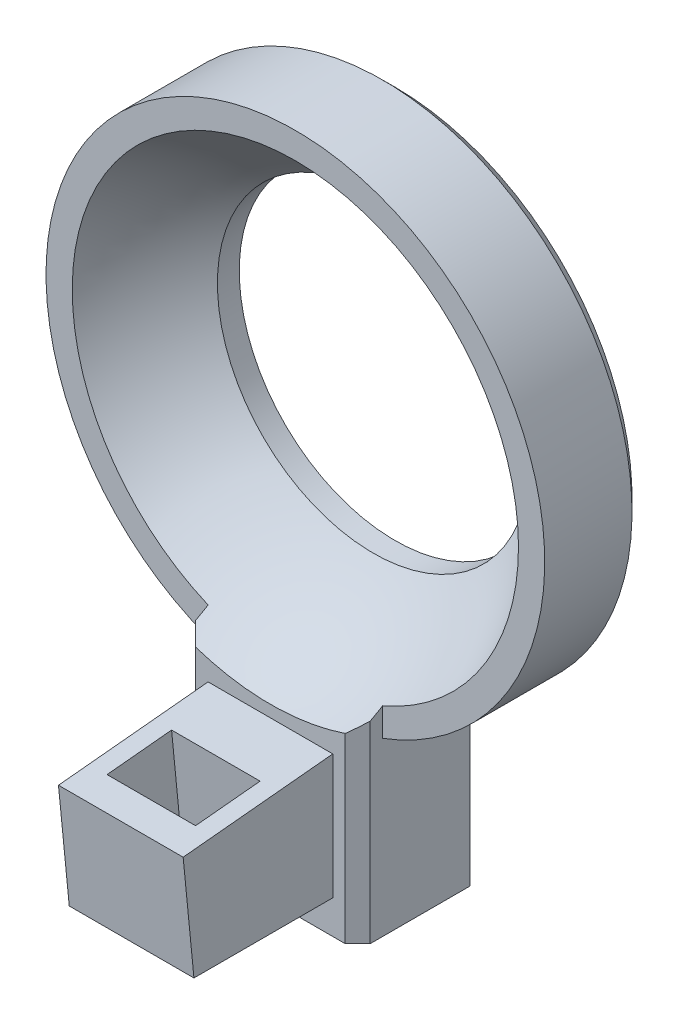
SolidWorks part; units mm, degrees
material "ABS"
ref_plane "Front Plane" through (0, 0, 0) normal (0, 0, 1) x (1, 0, 0)
ref_plane "Top Plane" through (0, 0, 0) normal (0, 1, 0) x (1, 0, 0)
ref_plane "Right Plane" through (0, 0, 0) normal (1, 0, 0) x (0, 0, -1)
sketch "Sketch1" plane through (0, 0, 0) normal (0, 0, 1) x (1, 0, 0)
  circle A0 centre (0, 0) radius 12.5
  circle A1 centre (0, 0) radius 20
  dimension "D1" = 40
  dimension "D2" = 25
extrude "Boss-Extrude1" add sketch "Sketch1" along normal blind 8
ref_axis "Axis1" through (0, 0, 8) along (0, 0, -1)
sketch "Sketch3" plane through (0, 0, 0) normal (0, 0, 1) x (1, 0, 0)
  line L0 (0, 0) -> (0, -32.5) construction
  line L1 (-7, -18.735) -> (-7, -32.5)
  line L2 (-7, -32.5) -> (7, -32.5)
  line L3 (7, -18.735) -> (7, -32.5)
  line L4 (-7, -18.735) -> (-7, -15.235)
  line L5 (-7, -15.235) -> (7, -15.235)
  line L6 (7, -15.235) -> (7, -18.735)
  circle A0 centre (0, 0) radius 20 construction
  dimension "D1" = 32.5
  dimension "D2" = 14
  dimension "D3" = 3.5
extrude "Boss-Extrude2" add sketch "Sketch3" along normal blind 10
sketch "Sketch2" plane through (0, 0, 0) normal (0, 1, 0) x (1, 0, 0)
  line L0 (0, -8) -> (0, 0) construction
  line L1 (0, -38.5) -> (0, 2.5)
  arc A0 (0, 2.5) -> (0, -38.5) centre (0, -18) ccw
  dimension "D1" = 41
  dimension "D2" = 18
revolve "Cut-Revolve2" cut sketch "Sketch2" angle 360 about axis through (0, 0, 8) along (0, 0, -1)
sketch "Sketch4" plane through (0, -32.5, 0) normal (0, -1, 0) x (1, 0, 0)
  line L0 (0, 10) -> (0, 0) construction
  line L8 (-7, 10) -> (7, 10) construction
  line L10 (-3.15, 8.15) -> (3.15, 8.15)
  line L11 (-3.15, 8.15) -> (-3.15, 1.85)
  line L12 (-3.15, 1.85) -> (3.15, 1.85)
  line L13 (3.15, 8.15) -> (3.15, 1.85)
  line L16 (-3.15, 8.15) -> (3.15, 1.85) construction
  line L17 (-3.15, 1.85) -> (3.15, 8.15) construction
  point P4 (0, 5)
  dimension "D1" = 6.3
extrude "Cut-Extrude1" cut sketch "Sketch4" against normal blind 12
sketch "Sketch11" plane through (0, 0, 0) normal (1, 0, 0) x (0, 0, -1)
  line L1 (-10, -19.814) -> (-22, -20.9904)
  line L2 (-22, -20.9904) -> (-21.135, -29.814)
  line L3 (-21.135, -29.814) -> (-10, -29.814)
  line L4 (-10, -29.814) -> (-10, -19.814)
  line L5 (-10, -32.5) -> (-10, -17.5285) construction
  line L6 (-8, 20) -> (-8, -18.735) construction
  circle A0 centre (-18, 0) radius 20.5 construction
  point P8 (-16, -20.4022)
  dimension "D1" = 41
  dimension "D2" = 10
  dimension "D3" = 6
  dimension "D4" = 12
  dimension "D5" = 10
extrude "Boss-Extrude4" add sketch "Sketch11" along normal mid plane 10
sketch "Sketch12" plane through (0, 0, 0) normal (1, 0, 0) x (0, 0, -1)
  circle A0 centre (-20, 0) radius 20.5 construction
  dimension "D2" = 41
  dimension "D1" = 10
ref_point "Point1"
sketch "Sketch13" plane through (0, -18.6545, -1.8287) normal (0, 0.9952, 0.0976) x (1, 0, 0)
  line L1 (-3.55, -16.2847) -> (3.55, -16.2847)
  line L2 (-3.55, -16.2847) -> (-3.55, -21.4847)
  line L3 (-3.55, -21.4847) -> (3.55, -21.4847)
  line L4 (3.55, -16.2847) -> (3.55, -21.4847)
  line L5 (-3.55, -16.2847) -> (3.55, -21.4847) construction
  line L6 (-3.55, -21.4847) -> (3.55, -16.2847) construction
  point P0 (0, -18.8847)
  dimension "D1" = 7.1
  dimension "D2" = 5.2
  dimension "D3" = 18.8847
extrude "Cut-Extrude5" cut sketch "Sketch13" against normal through all
chamfer "Chamfer1" distance 1 angle 45 5 edges at (7, -25.6175, 0) (-7, -25.6175, 0) (0, 20, 0) (-7, -25.0143, 10) (7, -25.0143, 10)
